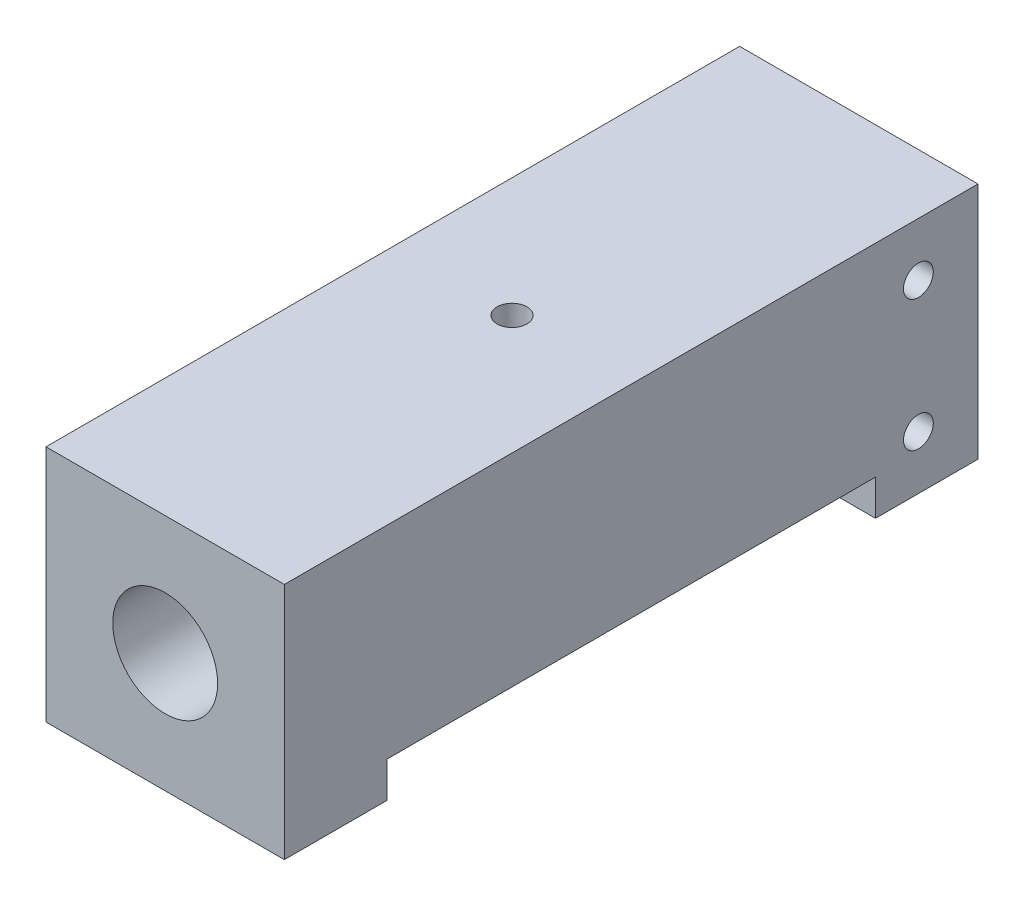
SolidWorks part; units mm, degrees
material "6063-T5"
ref_plane "Piano frontale" through (0, 0, 0) normal (0, 0, 1) x (1, 0, 0)
ref_plane "Piano superiore" through (0, 0, 0) normal (0, 1, 0) x (1, 0, 0)
ref_plane "Piano destro" through (0, 0, 0) normal (1, 0, 0) x (0, 0, -1)
sketch "Schizzo1" plane through (0, 0, 0) normal (0, 0, 1) x (1, 0, 0)
  line L1 (10, -10) -> (-10, -10)
  line L2 (10, -10) -> (10, 10)
  line L3 (10, 10) -> (-10, 10)
  line L4 (-10, -10) -> (-10, 10)
  line L5 (10, -10) -> (-10, 10) construction
  line L6 (10, 10) -> (-10, -10) construction
  point P0 (0, 0)
  dimension "D1" = 20
  dimension "D2" = 20
extrude "Estrusione-Estrusione1" add sketch "Schizzo1" against normal blind 58.2
sketch "Schizzo2" plane through (0, 0, -58.2) normal (0, 0, -1) x (-1, 0, 0)
  circle A0 centre (0, 0) radius 3
  dimension "D1" = 6
extrude "Taglio-Estrusione1" cut sketch "Schizzo2" against normal through all
sketch "Schizzo3" plane through (0, 0, -58.2) normal (0, 0, -1) x (-1, 0, 0)
  point P0 (0, 0)
hole_wizard "Foro filettato G1/8-1" positions "Schizzo8" profile "Schizzo7" tap size "G1/8" standard "BSI"
sketch "Schizzo8" plane through (0, 0, 0) normal (0, 0, 1) x (1, 0, 0)
  point P0 (0, 0)
sketch "Schizzo7" plane through (0, 0, 0) normal (1, 0, 0) x (0, -1, 0)
  line L0 (0, 0) -> (0, 12.6438)
  line L1 (0, 12.6438) -> (4.4, 10)
  line L2 (4.4, 10) -> (4.4, 0)
  line L5 (4.4, 0) -> (0, 0)
  line L10 (0, 12.6438) -> (-4.4, 10) construction
  line L11 (0, -6.35) -> (0, 107.95) construction
  dimension "Tap Drill Dia." = 8.8
  dimension "Tap Drill Depth" = 10
  dimension "Drill Angle" = 118
sketch "Schizzo11" plane through (0, 10, 0) normal (0, 1, 0) x (1, 0, 0)
  line L0 (0, 58.2) -> (0, 0) construction
  line L1 (10, 58.2) -> (-10, 58.2) construction
  line L2 (10, 29.1) -> (-10, 29.1) construction
  line L3 (10, 58.2) -> (10, 0) construction
  point P10 (0, 29.1)
  point P11 (0, 29.1)
  point P12 (0, 29.1)
hole_wizard "M3 Tapped Hole2" positions "Schizzo3D1" profile "Schizzo12" tap size "M3" standard "DIN"
sketch3d "Schizzo3D1"
  point P0 (0, 10, -29.1)
sketch "Schizzo12" plane through (0, 10, -29.1) normal (1, 0, 0) x (0, 0, 1)
  line L0 (0, 0) -> (0, 5.7511)
  line L1 (0, 5.7511) -> (1.25, 5)
  line L2 (1.25, 5) -> (1.25, 0)
  line L5 (1.25, 0) -> (0, 0)
  line L10 (0, 5.7511) -> (-1.25, 5) construction
  line L11 (0, -6.35) -> (0, 107.95) construction
  dimension "Tap Drill Dia." = 2.5
  dimension "Tap Drill Depth" = 5
  dimension "Drill Angle" = 118
cosmetic thread "Hole Thread4" parameters "D1"=5, "D2"=3
hole_wizard "Foro Ø16.0 (16)-1" positions "Schizzo3D3" profile "Schizzo14" hole size "Ø16.0" standard "ISO"
sketch3d "Schizzo3D3"
  point P0 (0, 0, 0)
  point P3 (0, 0, -58.2)
sketch "Schizzo14" plane through (0, 0, -58.2) normal (1, 0, 0) x (0, 1, 0)
  line L0 (0, 0) -> (0, 16.8069)
  line L1 (0, 16.8069) -> (8, 12)
  line L2 (8, 12) -> (8, 0)
  line L5 (8, 0) -> (0, 0)
  line L10 (0, 16.8069) -> (-8, 12) construction
  line L11 (0, -6.35) -> (0, 107.95) construction
  dimension "Hole Dia." = 16
  dimension "Hole Depth" = 12
  dimension "Drill Angle" = 118
sketch "Schizzo15" plane through (10, 0, 0) normal (1, 0, 0) x (0, 0, -1)
  line L0 (46.2, 0) -> (58.2, 0) construction
  line L1 (46.2, 8) -> (46.2, -8) construction
  line L4 (58.2, -10) -> (58.2, 10) construction
  line L6 (58.2, -10) -> (0, -10) construction
  point P5 (53.2, -5.5)
  point P8 (53.2, 5.5)
  dimension "D1" = 5.5
  dimension "D2" = 7
  dimension "D3" = 5
  dimension "D4" = 4.5
hole_wizard "M3 Tapped Hole3" positions "Schizzo3D4" profile "Schizzo16" tap size "M3" standard "ISO" end condition through all
sketch3d "Schizzo3D4"
  point P0 (10, 5.5, -53.2)
  point P3 (10, -5.5, -53.2)
sketch "Schizzo16" plane through (10, 5.5, -53.2) normal (0, 1, 0) x (0, 0, -1)
  line L0 (0, 0) -> (0, 20)
  line L1 (0, 20) -> (1.25, 20)
  line L2 (1.25, 20) -> (1.25, 0)
  line L5 (1.25, 0) -> (0, 0)
  line L11 (0, -6.35) -> (0, 107.95) construction
  dimension "Thread Major Dia." = 2.5
  dimension "Thru Tap Drill Depth" = 20
sketch "Sketch1" plane through (-10, 0, 0) normal (-1, 0, 0) x (0, 0, 1)
  line L0 (-58.2, 10) -> (-58.2, -10) construction
  line L1 (-58.2, 3) -> (-22, 3)
  line L2 (-58.2, 3) -> (-58.2, -3)
  line L3 (-58.2, -3) -> (-22, -3)
  line L4 (-22, 3) -> (-22, -3)
  line L5 (0, 10) -> (0, -10) construction
  line L6 (0, 0) -> (-22, 0) construction
  point P8 (-22, 0)
  dimension "D1" = 6
  dimension "D2" = 22
extrude "Boss-Extrude1" add sketch "Sketch1" along normal blind 4.9
sketch "Sketch2" plane through (10, 0, 0) normal (1, 0, 0) x (0, 0, -1)
  line L0 (58.2, -10) -> (0, -10) construction
  line L1 (49.6, -10) -> (33.6, -10)
  line L2 (49.6, -10) -> (49.6, -7)
  line L3 (49.6, -7) -> (33.6, -7)
  line L4 (33.6, -7) -> (8.6, -7)
  line L5 (41.6, -7) -> (41.6, -13) construction
  line L6 (8.6, -7) -> (8.6, -10)
  line L7 (8.6, -10) -> (33.6, -10)
  line L8 (0, -10) -> (8.6, -10) construction
  line L9 (49.6, -10) -> (58.2, -10) construction
  circle A2 centre (41.6, -13) radius 4 construction
  dimension "D1" = 16
  dimension "D2" = 3
extrude "Cut-Extrude1" cut sketch "Sketch2" against normal through all
sketch "Sketch3" plane through (0, 0, -22) normal (0, 0, 1) x (1, 0, 0)
  point P0 (-13, 0)
hole_wizard "M3 Tapped Hole4" positions "Sketch6" profile "Sketch7" tap size "M3" standard "ISO"
sketch "Sketch6" plane through (0, 0, -22) normal (0, 0, 1) x (1, 0, 0)
  point P0 (-13, 0)
sketch "Sketch7" plane through (-13, 0, -22) normal (1, 0, 0) x (0, -1, 0)
  line L0 (0, 0) -> (0, 20.7511)
  line L1 (0, 20.7511) -> (1.25, 20)
  line L2 (1.25, 20) -> (1.25, 0)
  line L5 (1.25, 0) -> (0, 0)
  line L10 (0, 20.7511) -> (-1.25, 20) construction
  line L11 (0, -6.35) -> (0, 107.95) construction
  dimension "Tap Drill Dia." = 2.5
  dimension "Tap Drill Depth" = 20
  dimension "Drill Angle" = 118
